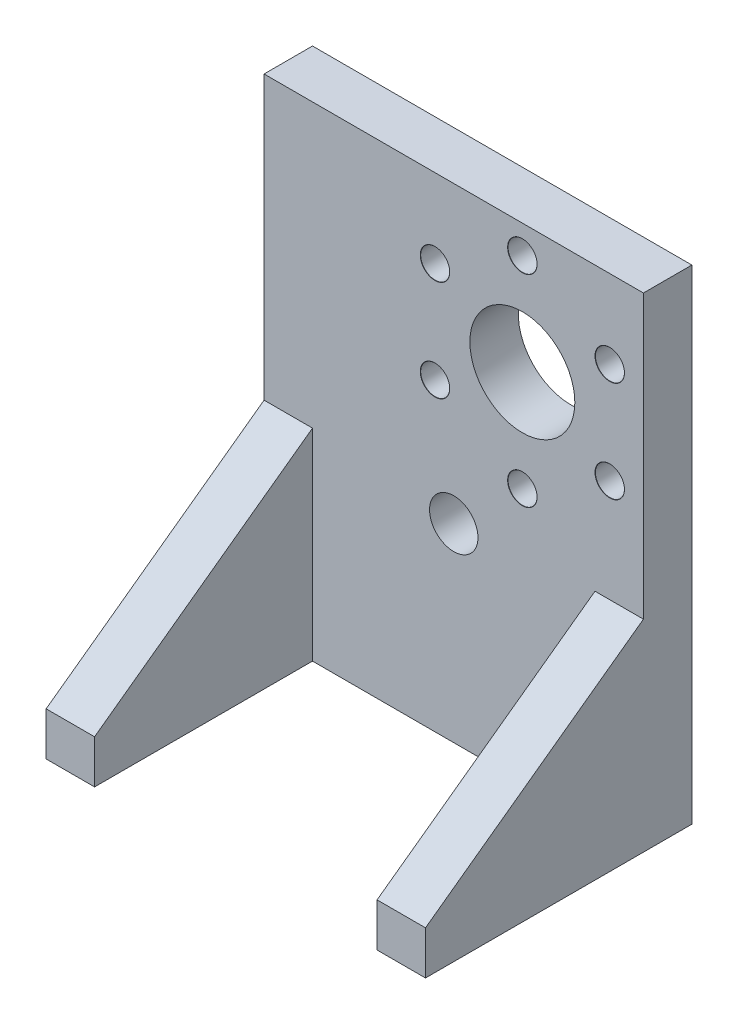
SolidWorks part; units mm, degrees
ref_plane "Front Plane" through (0, 0, 0) normal (0, 0, 1) x (1, 0, 0)
ref_plane "Top Plane" through (0, 0, 0) normal (0, 1, 0) x (1, 0, 0)
ref_plane "Right Plane" through (0, 0, 0) normal (1, 0, 0) x (0, 0, -1)
sketch "Sketch1" plane through (0, 0, 0) normal (0, 1, 0) x (1, 0, 0)
  line L0 (-17.5, 0) -> (17.5, 0)
  line L1 (17.5, 0) -> (17.5, -27)
  line L2 (17.5, -27) -> (23.5, -27)
  line L3 (23.5, -27) -> (23.5, 6)
  line L4 (23.5, 6) -> (-23.5, 6)
  line L5 (-23.5, 6) -> (-23.5, -27)
  line L6 (-23.5, -27) -> (-17.5, -27)
  line L7 (-17.5, -27) -> (-17.5, 0)
  line L8 (-17.5, 0) -> (-23.5, 0)
  line L9 (17.5, 0) -> (23.5, 0)
  line L10 (-20.5, -15) -> (-20.5, 3) construction
  line L11 (-20.5, 3) -> (20.5, 3) construction
  line L12 (20.5, 3) -> (20.5, -15) construction
  point P8 (0, 0)
  point P12 (-20.5, -15)
  point P13 (20.5, -15)
  point P14 (20.5, 3)
  point P15 (-20.5, 3)
  dimension "D1" = 6
  dimension "D2" = 6
  dimension "D3" = 6
  dimension "D4" = 35
  dimension "D5" = 27
  dimension "D6" = 18
extrude "Boss-Extrude1" add sketch "Sketch1" along normal blind 5 contours L7 L8 L5 L6 | L0 L9 L3 L4 L5 L8 | L9 L1 L2 L3 region at (0, 0, -3) region at (-20.5, 0, 13.5) region at (20.5, 0, 13.5)
extrude "Boss-Extrude2" add sketch "Sketch1<3>" along normal blind 55 from surface contours L0 L9 L3 L4 L5 L8 region at (0, 0, -3) starting at face at (0, 5, 12)
sketch "Sketch1<3>" plane through (0, 0, 0) normal (0, 1, 0) x (1, 0, 0) same geometry as "Sketch1"
ref_plane "Plane1" through (-23.5, 5, 0) normal (-1, 0, 0) x (0, 0, 1)
chamfer "Chamfer1" distance 20 angle 54 2 edges at (20.5, 5, 0) (-20.5, 5, 0) first distance on face at (0, 17.5, 0)
sketch "Sketch4" plane through (0, 0, 0) normal (0, 0, 1) x (1, 0, 0)
  line L1 (-17.5, 0) -> (17.5, 0) construction
  line L2 (23.5, 60) -> (23.5, 25) construction
  circle A0 centre (8.5, 44) radius 12.5 construction
  circle A1 centre (8.5, 44) radius 6.5
  point P0 (8.5, 44)
  point P7 (8.5, 56.5)
  point P11 (19.3253, 50.25)
  point P12 (19.3253, 37.75)
  point P13 (8.5, 31.5)
  point P14 (-2.3253, 37.75)
  point P15 (-2.3253, 50.25)
  point P16 (8.5, 44)
  dimension "D3" = 25
  dimension "D5" = 13
  dimension "D1" = 15
  dimension "D2" = 44
  dimension "D4" = 6
hole_wizard "M3 Clearance Hole1" positions "Sketch5" profile "Sketch6" hole size "M3" standard "ISO" end condition through all
sketch "Sketch5" plane through (0, 0, 0) normal (0, 0, 1) x (1, 0, 0)
  point P0 (8.5, 56.5)
  point P3 (19.3253, 50.25)
  point P6 (19.3253, 37.75)
  point P9 (8.5, 31.5)
  point P12 (-2.3253, 37.75)
  point P15 (-2.3253, 50.25)
sketch "Sketch6" plane through (8.5, 56.5, 0) normal (1, 0, 0) x (0, -1, 0)
  line L0 (0, 0) -> (0, 6)
  line L1 (0, 6) -> (1.8, 6)
  line L2 (1.8, 6) -> (1.8, 0.025)
  line L3 (1.8, 0.025) -> (1.825, 0)
  line L5 (1.825, 0) -> (0, 0)
  line L6 (-1.8, 0.025) -> (-1.825, 0) construction
  line L11 (0, -6.35) -> (0, 107.95) construction
  dimension "Thru Hole Dia." = 3.6
  dimension "Thru Hole Depth" = 6
  dimension "Near C'Sink Dia." = 3.65
  dimension "Near C'Sink Angle" = 90
extrude "Cut-Extrude1" cut sketch "Sketch4" against normal through all both and the other way through all
hole_wizard "Ø5.3 (5.3) Diameter Hole1" positions "Sketch7" profile "Sketch9" hole size "Ø5.3" standard "ISO"
sketch "Sketch7" plane through (0, 0, 0) normal (0, -1, 0) x (-1, 0, 0)
  point P0 (-20.5, 3)
  point P3 (-20.5, -15)
  point P6 (20.5, 3)
  point P9 (20.5, -15)
sketch "Sketch9" plane through (20.5, 0, -3) normal (1, 0, 0) x (0, 0, -1)
  line L0 (0, 0) -> (0, 8.5923)
  line L1 (0, 8.5923) -> (2.65, 7)
  line L2 (2.65, 7) -> (2.65, 0)
  line L5 (2.65, 0) -> (0, 0)
  line L10 (0, 8.5923) -> (-2.65, 7) construction
  line L11 (0, -6.35) -> (0, 107.95) construction
  dimension "Hole Dia." = 5.3
  dimension "Hole Depth" = 7
  dimension "Drill Angle" = 118
sketch "Sketch10" plane through (0, 0, 0) normal (0, 0, 1) x (1, 0, 0)
  line L0 (-17.5, 0) -> (17.5, 0) construction
  circle A0 centre (0, 23.5) radius 3
  dimension "D2" = 6
  dimension "D1" = 23.5
extrude "Cut-Extrude2" cut sketch "Sketch10" against normal blind 10
